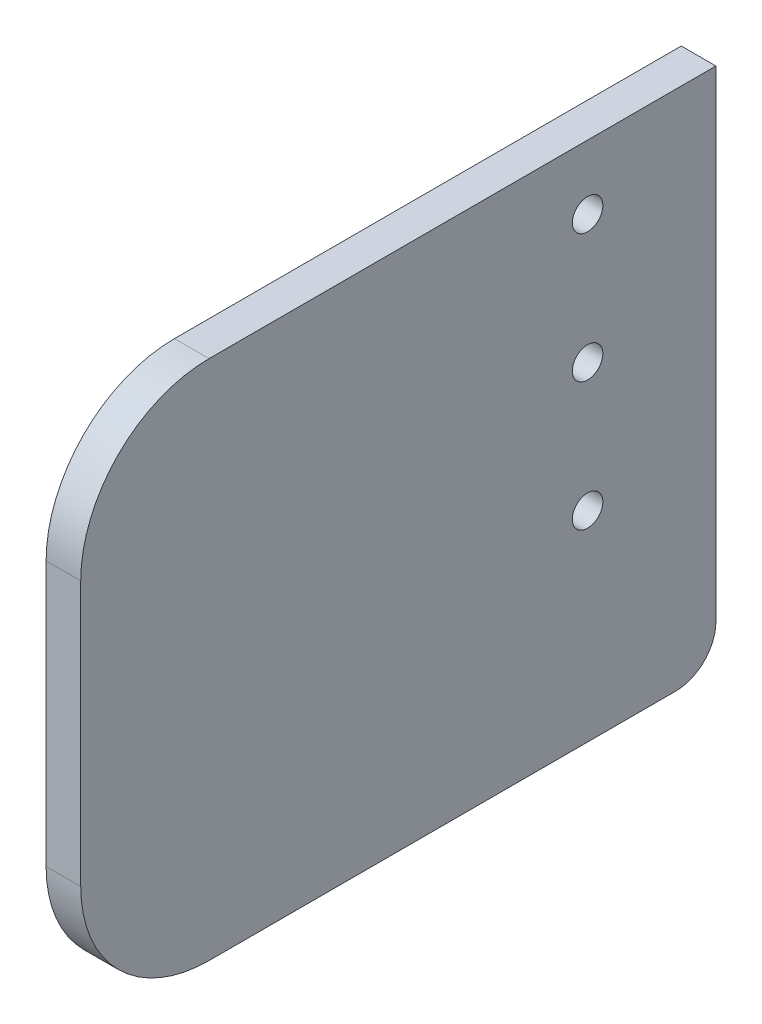
SolidWorks part; units mm, degrees
material "Acrylic (Medium-high impact)"
ref_plane "Front" through (0, 0, 0) normal (0, 0, 1) x (1, 0, 0)
ref_plane "Top" through (0, 0, 0) normal (0, 1, 0) x (1, 0, 0)
ref_plane "Right" through (0, 0, 0) normal (1, 0, 0) x (0, 0, -1)
ref_axis "side-side" through (80.9, 0, 0) along (-1, 0, 0)
ref_axis "up-down" through (0, 50, 0) along (0, -1, 0)
ref_axis "front-back" through (0, 0, -80.9) along (0, 0, 1)
sketch "Sketch2" plane through (0, 0, 0) normal (1, 0, 0) x (0, 0, -1)
  point P0 (79.196, 65)
sketch "Sketch1" plane through (0, 0, 0) normal (1, 0, 0) x (0, 0, -1)
  line L0 (63.196, 57) -> (63.196, 41) construction
  line L1 (16, 0) -> (74.196, 0)
  line L2 (0, 16) -> (0, 49)
  line L3 (16, 65) -> (79.196, 65)
  line L4 (79.196, 5) -> (79.196, 65)
  arc A0 (0, 49) -> (16, 65) centre (16, 49) cw
  arc A1 (16, 0) -> (0, 16) centre (16, 16) cw
  arc A2 (74.196, 0) -> (79.196, 5) centre (74.196, 5) ccw
  circle A3 centre (63.196, 57) radius 1.905
  circle A4 centre (63.196, 41) radius 1.905
  circle A5 centre (63.196, 25) radius 1.905
  point P9 (0, 0)
  point P13 (0, 65)
  point P20 (63.196, 49)
  dimension "D1" = 16
  dimension "D2" = 5
  dimension "D5" = 3.81
  dimension "D10" = 16
  dimension "D3" = 65
  dimension "D4" = 79.196
  dimension "D6" = 16
  dimension "D7" = 16
  dimension "D8" = 16
  dimension "D9" = 16
extrude "Boss-Extrude1" add sketch "Sketch1" against normal blind 4.318
